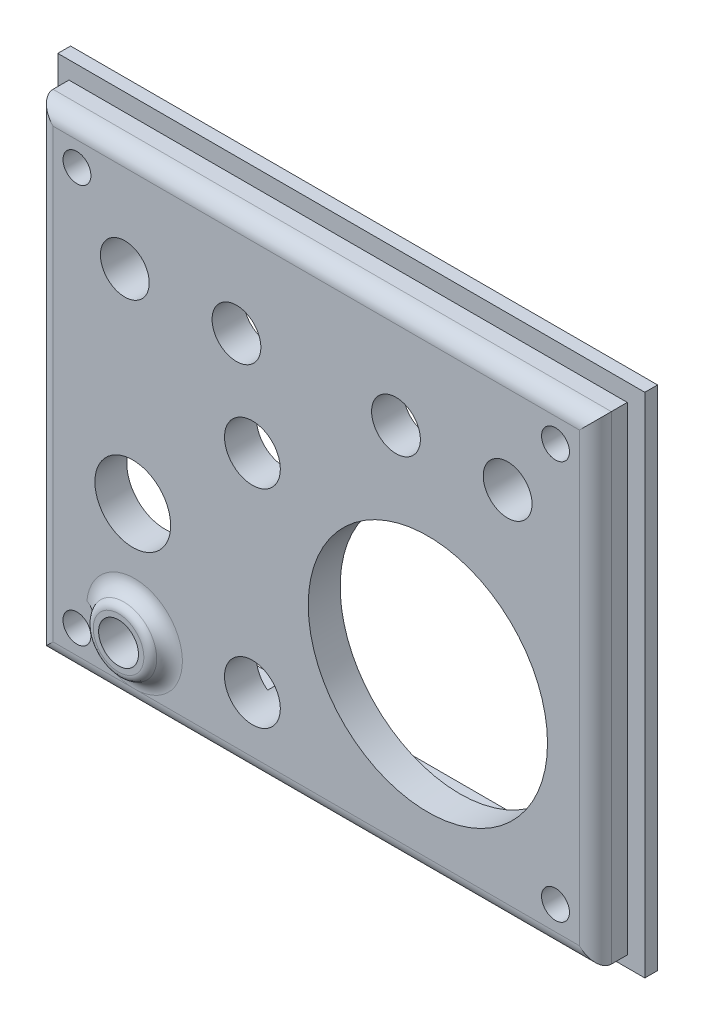
SolidWorks part; units mm, degrees
ref_plane "Спереди" through (0, 0, 0) normal (0, 0, 1) x (1, 0, 0)
ref_plane "Сверху" through (0, 0, 0) normal (0, 1, 0) x (1, 0, 0)
ref_plane "Справа" through (0, 0, 0) normal (1, 0, 0) x (0, 0, -1)
sketch "Sketch1" plane through (0, 0, 0) normal (0, 0, 1) x (1, 0, 0)
  line L1 (35, -30) -> (-35, -30)
  line L2 (35, -30) -> (35, 30)
  line L3 (35, 30) -> (-35, 30)
  line L4 (-35, -30) -> (-35, 30)
  line L5 (35, -30) -> (-35, 30) construction
  line L6 (35, 30) -> (-35, -30) construction
  point P0 (0, 0)
  dimension "D1" = 70
  dimension "D2" = 60
extrude "Boss-Extrude1" add sketch "Sketch1" along normal blind 4
sketch "Sketch2" plane through (0, 0, 0) normal (0, 0, -1) x (-1, 0, 0)
  line L0 (35, -30) -> (-35, -30) construction
  line L1 (-31.8, 26.8) -> (31.8, 26.8)
  line L2 (-31.8, 26.8) -> (-31.8, -26.8)
  line L3 (-31.8, -26.8) -> (31.8, -26.8)
  line L4 (31.8, 26.8) -> (31.8, -26.8)
  line L5 (-31.8, 26.8) -> (31.8, -26.8) construction
  line L6 (-31.8, -26.8) -> (31.8, 26.8) construction
  line L7 (-35, -30) -> (-35, 30) construction
  line L9 (28.8, -23.8) -> (-28.8, -23.8)
  line L10 (28.8, -23.8) -> (28.8, 23.8)
  line L11 (28.8, 23.8) -> (-28.8, 23.8)
  line L12 (-28.8, -23.8) -> (-28.8, 23.8)
  line L13 (28.8, -23.8) -> (-28.8, 23.8) construction
  line L14 (28.8, 23.8) -> (-28.8, -23.8) construction
  point P0 (0, 0)
  point P10 (0, 0)
  dimension "D1" = 3.2
  dimension "D2" = 3.2
  dimension "D3" = 3
  dimension "D4" = 3
extrude "Boss-Extrude2" add sketch "Sketch2" along normal blind 2
chamfer "Chamfer1" distance 0.5 angle 70 4 edges at (-31.8, 0, -2) (0, 26.8, -2) (31.8, 0, -2) (0, -26.8, -2) first distance on face at (0, 0, -2)
fillet "Fillet1" radius 2 4 edges at (0, 30, 4) (35, 0, 4) (0, -30, 4) (-35, 0, 4)
sketch "Sketch3" plane through (0, 0, 4) normal (0, 0, 1) x (1, 0, 0)
  line L0 (0, -41.7208) -> (0, 41.7208) construction
  line L1 (33, 17) -> (-33, 17) construction
  line L2 (-33, 28) -> (-33, -28) construction
  circle A1 centre (-24, 17) radius 3.0603
  circle A2 centre (10, 17) radius 3.0603
  circle A4 centre (-10, 17) radius 3.0603
  circle A5 centre (24, 17) radius 3.0603
  point P0 (-21.1757, 17)
  point P4 (0, 0)
  point P11 (0, 17)
  point P13 (-10, 17)
  dimension "D1" = 14
  dimension "D2" = 17
  dimension "D3" = 20
  dimension "D4" = 10
  dimension "D7" = 14
extrude "Cut-Extrude1" cut sketch "Sketch3" against normal through all
sketch "Sketch4" plane through (0, 0, 4) normal (0, 0, 1) x (1, 0, 0)
  line L0 (0, -40.1993) -> (0, 40.1993) construction
  line L1 (0, 0) -> (33, 0) construction
  line L2 (33, -28) -> (33, 28) construction
  line L3 (14, -8) -> (0, -8) construction
  circle A0 centre (14, -8) radius 15
  point P3 (0, 0)
  dimension "D1" = 30
  dimension "D2" = 8
  dimension "D3" = 14
extrude "Cut-Extrude2" cut sketch "Sketch4" against normal through all
sketch "Sketch5" plane through (0, 0, 4) normal (0, 0, 1) x (1, 0, 0)
  line L0 (-8, 28) -> (-8, -28) construction
  line L1 (33, 28) -> (-33, 28) construction
  line L2 (-33, -28) -> (33, -28) construction
  line L3 (14, -8) -> (-8, -8) construction
  line L4 (14, -8) -> (14, 28) construction
  circle A0 centre (-8, 5) radius 3.5
  circle A1 centre (-8, -21) radius 3.5
  dimension "D1" = 26
  dimension "D2" = 7
  dimension "D3" = 13
  dimension "D4" = 22
extrude "Cut-Extrude3" cut sketch "Sketch5" against normal through all
sketch "Sketch6" plane through (0, 0, 0) normal (0, 0, -1) x (-1, 0, 0)
  circle A0 centre (24, 17) radius 5
  circle A1 centre (-24, 17) radius 5
  circle A2 centre (-24, 17) radius 3.0603
  circle A3 centre (24, 17) radius 3.0603
  dimension "D1" = 10
extrude "Boss-Extrude3" add sketch "Sketch6" along normal blind 2
fillet "Fillet2" radius 1 3 edges at (28.8, 23.8, -1) (28.8, 18.4, -1) (28.8, 15.6, -1)
sketch "Sketch7" plane through (0, 0, -2) normal (0, 0, -1) x (-1, 0, 0)
  line L0 (15, 27.7408) -> (15, -32.2592)
  line L2 (15, -32.2592) -> (35, -32.2592)
  line L3 (35, -32.2592) -> (35, 27.7408)
  line L4 (35, 27.7408) -> (15, 27.7408)
  line L5 (35, 30) -> (35, -30) construction
  dimension "D1" = 20
  dimension "D2" = 60
extrude "Cut-Extrude4" cut sketch "Sketch7" against normal up to surface (2 mm away) up to face at (0, 0, 0)
sketch "Sketch8" plane through (0, 0, 0) normal (0, 0, -1) x (-1, 0, 0)
  line L0 (23, 30) -> (23, -30) construction
  line L1 (-35, 30) -> (35, 30) construction
  line L2 (35, -30) -> (-35, -30) construction
  line L3 (35, 30) -> (35, -30) construction
  line L4 (-14, -8) -> (23, -8) construction
  circle A0 centre (23, -8) radius 4.75
  point P13 (0, 0)
  dimension "D1" = 9.5
  dimension "D2" = 12
extrude "Cut-Extrude5" cut sketch "Sketch8" against normal through all
sketch "Sketch9" plane through (0, 0, 0) normal (0, 0, -1) x (-1, 0, 0)
  line L0 (35, 30) -> (35, -30) construction
  line L1 (-30, -25) -> (30, -25) construction
  line L2 (-30, -25) -> (-30, 25) construction
  line L3 (-30, 25) -> (30, 25) construction
  line L4 (30, -25) -> (30, 25) construction
  line L5 (-30, -25) -> (30, 25) construction
  line L6 (-30, 25) -> (30, -25) construction
  line L7 (35, -30) -> (-35, -30) construction
  circle A0 centre (30, 25) radius 1.75
  circle A1 centre (30, -25) radius 1.75
  circle A2 centre (-30, -25) radius 1.75
  circle A3 centre (-30, 25) radius 1.75
  point P0 (0, 0)
  dimension "D3" = 3.5
  dimension "D1" = 5
  dimension "D2" = 5
extrude "Cut-Extrude6" cut sketch "Sketch9" against normal through all both and the other way through all
sketch "Sketch10" plane through (0, 0, 0) normal (0, 0, -1) x (-1, 0, 0)
  line L0 (23, -8) -> (23, 1) construction
  circle A0 centre (23, 1) radius 2
  dimension "D2" = 4
  dimension "D1" = 9
extrude "Cut-Extrude7" cut sketch "Sketch10" against normal blind 2
sketch "Sketch11" plane through (0, 0, 0) normal (0, 0, -1) x (-1, 0, 0)
  circle A0 centre (24, 17) radius 5
  circle A1 centre (24, 17) radius 3.0603
  arc A2 (-27.1667, 13.1306) -> (-27.1667, 20.8694) centre (-24, 17) ccw construction
  circle A3 centre (-24, 17) radius 3.0603 construction
extrude "Boss-Extrude4" add sketch "Sketch11" along normal up to surface (2 mm away) up to face at (1.8381, -24.7536, -2)
sketch "Sketch12" plane through (0, 0, 0) normal (0, 0, -1) x (-1, 0, 0)
  circle A0 centre (-30, 25) radius 5
  circle A1 centre (-30, -25) radius 5
  dimension "D1" = 10
extrude "Cut-Extrude9" cut sketch "Sketch12" along normal through all
sketch "Sketch13" plane through (0, 0, 0) normal (0, 0, -1) x (-1, 0, 0)
  line L0 (35, -22) -> (-35, -22) construction
  line L1 (35, 30) -> (35, -30) construction
  line L2 (-35, -30) -> (-35, 30) construction
  line L3 (35, -30) -> (-35, -30) construction
  circle A0 centre (22.7832, -22) radius 2.5
  dimension "D1" = 5
  dimension "D2" = 8
extrude "Cut-Extrude10" cut sketch "Sketch13" against normal through all
sketch "Sketch14" plane through (0, 0, 0) normal (0, 0, -1) x (-1, 0, 0)
  line L1 (19.5332, -18.75) -> (26.0332, -18.75)
  line L2 (19.5332, -18.75) -> (19.5332, -25.25)
  line L3 (19.5332, -25.25) -> (26.0332, -25.25)
  line L4 (26.0332, -18.75) -> (26.0332, -25.25)
  line L5 (19.5332, -18.75) -> (26.0332, -25.25) construction
  line L6 (19.5332, -25.25) -> (26.0332, -18.75) construction
  line L7 (18.2832, -17.5) -> (27.2832, -17.5)
  line L8 (18.2832, -17.5) -> (18.2832, -26.5)
  line L9 (18.2832, -26.5) -> (27.2832, -26.5)
  line L10 (27.2832, -17.5) -> (27.2832, -26.5)
  line L11 (18.2832, -17.5) -> (27.2832, -26.5) construction
  line L12 (18.2832, -26.5) -> (27.2832, -17.5) construction
  point P0 (22.7832, -22)
  point P6 (22.7832, -22)
  dimension "D1" = 6.5
  dimension "D2" = 9
extrude "Boss-Extrude5" add sketch "Sketch14" along normal up to surface (2 mm away) up to face at (0.6932, -24.7503, -2)
sketch "Sketch17" plane through (0, 0, 4) normal (0, 0, 1) x (1, 0, 0)
  circle A0 centre (-22.7832, -22) radius 2.5
  circle A1 centre (-22.7832, -22) radius 4
  circle A2 centre (-22.7832, -22) radius 2.5 construction
  dimension "D1" = 8
extrude "Boss-Extrude7" add sketch "Sketch17" along normal blind 2
fillet "Fillet5" radius 2 1 edges at (-18.7832, -22, 4)
fillet "Fillet6" radius 1 1 edges at (-18.7832, -22, 6)
sketch "Sketch18" plane through (0, 0, 4) normal (0, 0, 1) x (1, 0, 0)
  circle A0 centre (-30, -25) radius 3.75
  dimension "D1" = 7.5
extrude "Cut-Extrude13" cut sketch "Sketch18" along normal through all
sketch "Sketch19" plane through (0, 0, 0) normal (0, 0, -1) x (-1, 0, 0)
  line L0 (-31.8, -20.3352) -> (-31.8, 20.3352) construction
  line L1 (32.8, 27.8) -> (-32.8, 27.8)
  line L2 (32.8, 27.8) -> (32.8, -27.8)
  line L3 (32.8, -27.8) -> (-32.8, -27.8)
  line L4 (-32.8, 27.8) -> (-32.8, -27.8)
  line L5 (32.8, 27.8) -> (-32.8, -27.8) construction
  line L6 (32.8, -27.8) -> (-32.8, 27.8) construction
  line L7 (-36.8, 31.8) -> (36.8, 31.8)
  line L8 (-36.8, 31.8) -> (-36.8, -31.8)
  line L9 (-36.8, -31.8) -> (36.8, -31.8)
  line L10 (36.8, 31.8) -> (36.8, -31.8)
  line L11 (-36.8, 31.8) -> (36.8, -31.8) construction
  line L12 (-36.8, -31.8) -> (36.8, 31.8) construction
  line L13 (-25.3352, -26.8) -> (15, -26.8) construction
  point P0 (0, 0)
  point P6 (0, 0)
  dimension "D1" = 1
  dimension "D2" = 4
  dimension "D3" = 4
  dimension "D4" = 1
extrude "Boss-Extrude8" add sketch "Sketch19" along normal up to surface (2 mm away) from offset 0.4 separate body up to face at (0.6932, -24.7503, -2)
sketch "Sketch20" plane through (0, 0, -2) normal (0, 0, -1) x (-1, 0, 0)
  line L0 (32.8, 27.8) -> (-32.8, 27.8) construction
  line L1 (32.8, -27.8) -> (32.8, 27.8) construction
  line L2 (-32.8, -27.8) -> (32.8, -27.8) construction
  line L3 (-32.8, 27.8) -> (-32.8, -27.8) construction
  line L4 (-27.2562, 27.8) -> (-32.8, 27.8)
  line L5 (-32.8, 27.8) -> (-32.8, 22.2562)
  line L6 (-32.8, -22.2562) -> (-32.8, -27.8)
  line L7 (-32.8, -27.8) -> (-27.2562, -27.8)
  line L8 (25.8802, 27.8) -> (32.8, 27.8)
  line L9 (32.8, 27.8) -> (32.8, 20.5583)
  line L10 (27.8424, -27.8) -> (27.8424, -21.5441)
  line L11 (32.8, -21.5441) -> (32.8, -27.8)
  line L12 (32.8, -27.8) -> (27.8424, -27.8)
  line L13 (27.8424, -21.5441) -> (32.8, -21.5441)
  arc A0 (25.8802, 27.8) -> (32.8, 20.5583) centre (34.3418, 28.9585) ccw
  arc A2 (-27.2562, 27.8) -> (-32.8, 22.2562) centre (-30.5342, 25.5342) cw
  arc A3 (-32.8, -22.2562) -> (-27.2562, -27.8) centre (-30.5342, -25.5342) cw
extrude "Boss-Extrude9" add sketch "Sketch20" against normal up to surface (1.6 mm away) up to face at (0, 0, -0.4)
